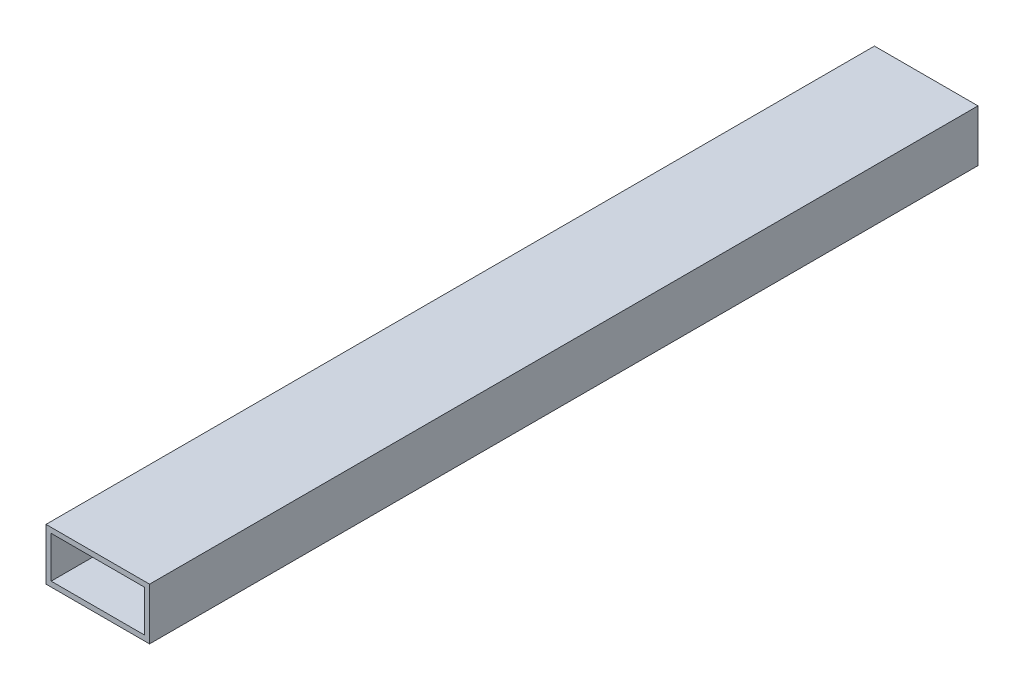
SolidWorks part; units mm, degrees
material "6061 Alloy"
ref_plane "Front Plane" through (0, 0, 0) normal (0, 0, 1) x (1, 0, 0)
ref_plane "Top Plane" through (0, 0, 0) normal (0, 1, 0) x (1, 0, 0)
ref_plane "Right Plane" through (0, 0, 0) normal (1, 0, 0) x (0, 0, -1)
sketch "Sketch1" plane through (0, 0, 0) normal (0, 0, 1) x (1, 0, 0)
  line L1 (-12.7, 6.35) -> (12.7, 6.35)
  line L2 (-12.7, 6.35) -> (-12.7, -6.35)
  line L3 (-12.7, -6.35) -> (12.7, -6.35)
  line L4 (12.7, 6.35) -> (12.7, -6.35)
  point P4 (-12.7, 0)
  point P6 (0, 6.35)
  dimension "D1" = 12.7
  dimension "D2" = 25.4
extrude "Boss-Extrude1" add sketch "Sketch1" along normal blind 203.2
sketch "Sketch4" plane through (0, 0, 0) normal (0, 0, -1) x (-1, 0, 0)
  line L0 (-12.7, -6.35) -> (-12.7, 6.35) construction
  line L1 (-11.43, 5.08) -> (11.43, 5.08)
  line L2 (-11.43, 5.08) -> (-11.43, -5.08)
  line L3 (-11.43, -5.08) -> (11.43, -5.08)
  line L4 (11.43, 5.08) -> (11.43, -5.08)
  line L5 (-12.7, 6.35) -> (12.7, 6.35) construction
  line L6 (12.7, -6.35) -> (-12.7, -6.35) construction
  line L7 (12.7, 6.35) -> (12.7, -6.35) construction
  dimension "D1" = 1.27
  dimension "D2" = 1.27
  dimension "D3" = 1.27
  dimension "D4" = 1.27
extrude "Cut-Extrude1" cut sketch "Sketch4" against normal through all
